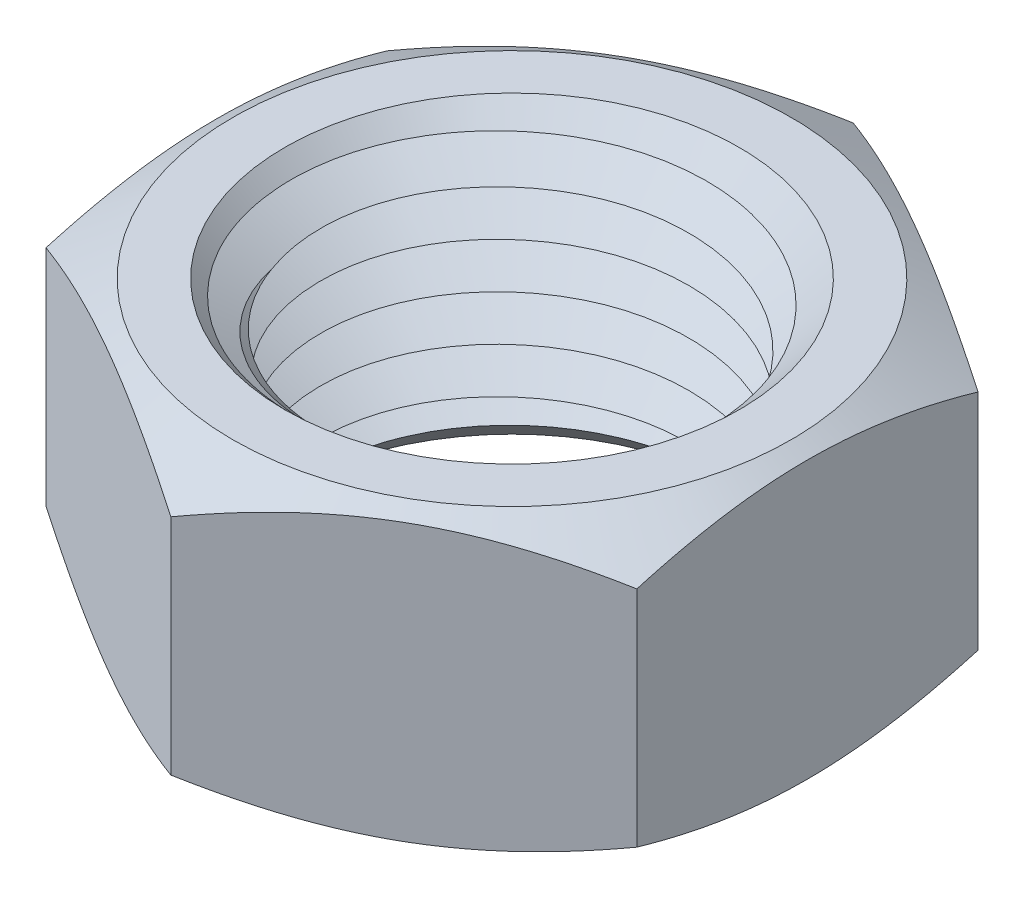
SolidWorks part; units mm, degrees
ref_plane "Plano frontal" through (0, 0, 0) normal (0, 0, 1) x (1, 0, 0)
ref_plane "Plano superior" through (0, 0, 0) normal (0, 1, 0) x (1, 0, 0)
ref_plane "Plano direito" through (0, 0, 0) normal (1, 0, 0) x (0, 0, -1)
sketch "Esboço1" plane through (0, 0, 0) normal (0, 1, 0) x (1, 0, 0)
  line L1 (0, 7.5056) -> (-6.5, 3.7528)
  line L2 (-6.5, 3.7528) -> (-6.5, -3.7528)
  line L3 (-6.5, -3.7528) -> (0, -7.5056)
  line L4 (0, -7.5056) -> (6.5, -3.7528)
  line L5 (6.5, -3.7528) -> (6.5, 3.7528)
  line L6 (6.5, 3.7528) -> (0, 7.5056)
  circle A0 centre (0, 0) radius 4
  circle A1 centre (0, 0) radius 6.5 construction
  dimension "D1" = 8
  dimension "D2" = 13
extrude "Extrusão1" add sketch "Esboço1" against normal blind 6.5
sketch "Esboço2" plane through (0, 0, 0) normal (0, 1, 0) x (1, 0, 0)
  circle A0 centre (0, 0) radius 6.143
extrude "Extrusão2" cut sketch "Esboço2" against normal blind 1 draft 60 flip side to cut
sketch "Esboço3" plane through (0, -6.5, 0) normal (0, -1, 0) x (1, 0, 0)
  circle A0 centre (0, 0) radius 6.1341
extrude "Extrusão3" cut sketch "Esboço3" against normal blind 1 draft 60 flip side to cut
sketch "Esboço4" plane through (0, 0, 0) normal (0, 1, 0) x (1, 0, 0)
  circle A0 centre (0, 0) radius 4 construction
  circle A1 centre (0, 0) radius 4
curve "Hélice/Espiral1" pitch 1 height 6.5 radius 4 centre (0, 0, 0) axis (0, -1, 0) start towards (0, 0, 1)
sketch "Esboço5" plane through (0, 0, 0) normal (0, 0, 1) x (1, 0, 0)
  line L0 (-4, 0) -> (-4, 1) construction
  line L1 (4, 0) -> (-4, 0) construction
  line L2 (-4, 1) -> (-4.866, 0.5) construction
  line L3 (-4.866, 0.5) -> (-4, 0) construction
  line L4 (-4, 0.5) -> (-5.0146, 0.5) construction
  line L5 (-3.97, -0.052) -> (-3.97, 1.052)
  line L6 (-3.97, 1.052) -> (-4.926, 0.5)
  line L7 (-4.926, 0.5) -> (-3.97, -0.052)
  spline S0 degree 3 poles (-4, 0) (-4, -0.0209) (-3.7876, -0.0632) (-2.8813, -0.1262) (-1.5279, -0.1893) (0.0626, -0.2524) (1.6434, -0.3155) (2.9692, -0.3786) (3.8342, -0.4417) (4.1043, -0.5049) (3.7375, -0.568) (2.7907, -0.6311) (1.4109, -0.6942) (-0.1878, -0.7573) (-1.7574, -0.8204) (-3.0543, -0.8835) (-3.8772, -0.9466) (-4.0986, -1.0097) (-3.6839, -1.0728) (-2.6976, -1.1359) (-1.2927, -1.199) (0.3128, -1.2621) (1.8698, -1.3252) (3.1366, -1.3883) (3.9167, -1.4515) (4.089, -1.5146) (3.6269, -1.5777) (2.6019, -1.6408) (1.1732, -1.7039) (-0.4375, -1.767) (-1.9804, -1.8301) (-3.2159, -1.8932) (-3.9525, -1.9563) (-4.0757, -2.0194) (-3.5665, -2.0825) (-2.5038, -2.1456) (-1.0527, -2.2087) (0.5618, -2.2718) (2.0891, -2.335) (3.2923, -2.3981) (3.9846, -2.4612) (4.0585, -2.5243) (3.5027, -2.5874) (2.4034, -2.6505) (0.9311, -2.7136) (-0.6856, -2.7767) (-2.196, -2.8398) (-3.3656, -2.9029) (-4.013, -2.966) (-4.0376, -3.0291) (-3.4358, -3.0922) (-2.3008, -3.1553) (-0.8088, -3.2184) (0.8088, -3.2816) (2.3008, -3.3447) (3.4358, -3.4078) (4.0376, -3.4709) (4.013, -3.534) (3.3656, -3.5971) (2.196, -3.6602) (0.6856, -3.7233) (-0.9311, -3.7864) (-2.4034, -3.8495) (-3.5027, -3.9126) (-4.0585, -3.9757) (-3.9846, -4.0388) (-3.2923, -4.1019) (-2.0891, -4.165) (-0.5618, -4.2282) (1.0527, -4.2913) (2.5038, -4.3544) (3.5665, -4.4175) (4.0757, -4.4806) (3.9525, -4.5437) (3.2159, -4.6068) (1.9804, -4.6699) (0.4375, -4.733) (-1.1732, -4.7961) (-2.6019, -4.8592) (-3.6269, -4.9223) (-4.089, -4.9854) (-3.9167, -5.0485) (-3.1366, -5.1117) (-1.8698, -5.1748) (-0.3128, -5.2379) (1.2927, -5.301) (2.6976, -5.3641) (3.6839, -5.4272) (4.0986, -5.4903) (3.8772, -5.5534) (3.0543, -5.6165) (1.7574, -5.6796) (0.1878, -5.7427) (-1.4109, -5.8058) (-2.7907, -5.8689) (-3.7375, -5.932) (-4.1043, -5.9951) (-3.8342, -6.0583) (-2.9692, -6.1214) (-1.6434, -6.1845) (-0.0626, -6.2476) (1.5279, -6.3107) (2.8813, -6.3738) (3.7876, -6.4368) (4, -6.4791) (4, -6.5) knots 0 0 0 0 0.009709 0.019417 0.029126 0.038835 0.048544 0.058252 0.067961 0.07767 0.087379 0.097087 0.106796 0.116505 0.126214 0.135922 0.145631 0.15534 0.165049 0.174757 0.184466 0.194175 0.203883 0.213592 0.223301 0.23301 0.242718 0.252427 0.262136 0.271845 0.281553 0.291262 0.300971 0.31068 0.320388 0.330097 0.339806 0.349515 0.359223 0.368932 0.378641 0.38835 0.398058 0.407767 0.417476 0.427184 0.436893 0.446602 0.456311 0.466019 0.475728 0.485437 0.495146 0.504854 0.514563 0.524272 0.533981 0.543689 0.553398 0.563107 0.572816 0.582524 0.592233 0.601942 0.61165 0.621359 0.631068 0.640777 0.650485 0.660194 0.669903 0.679612 0.68932 0.699029 0.708738 0.718447 0.728155 0.737864 0.747573 0.757282 0.76699 0.776699 0.786408 0.796117 0.805825 0.815534 0.825243 0.834951 0.84466 0.854369 0.864078 0.873786 0.883495 0.893204 0.902913 0.912621 0.92233 0.932039 0.941748 0.951456 0.961165 0.970874 0.980583 0.990291 1 1 1 1 construction
  dimension "D1" = 1
  dimension "D2" = 60
  dimension "D3" = 0.03
chamfer "Chanfro1" distance 1 angle 45 2 edges at (0, -6.5, 4) (0, 0, 4)
sweep "Varredura de corte2" cut profiles "Esboço5" path "Hélice/Espiral1"
